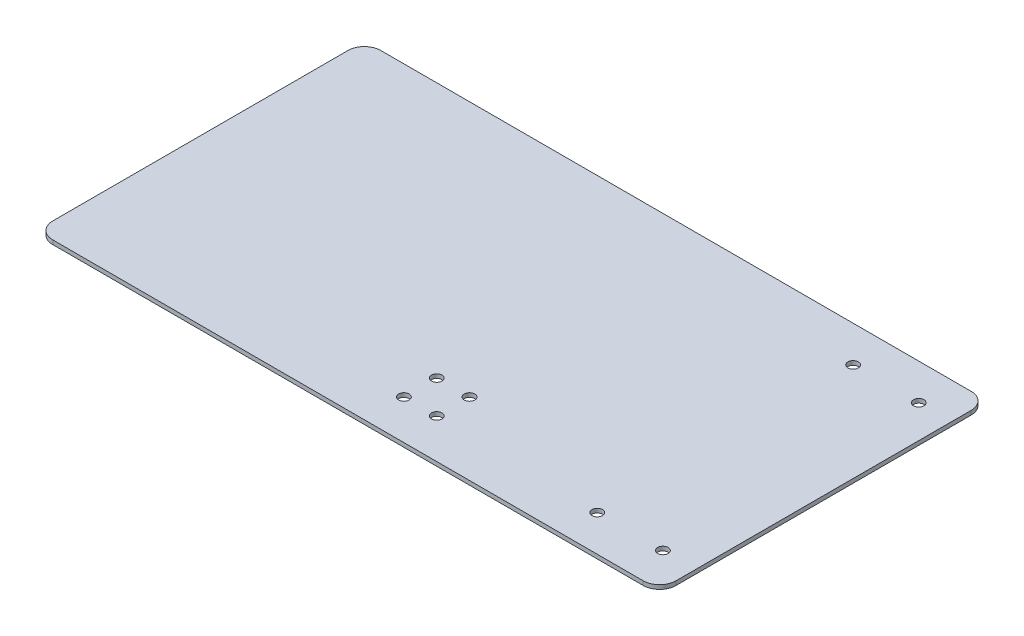
SolidWorks part; units mm, degrees
ref_plane "Front Plane" through (0, 0, 0) normal (0, 0, 1) x (1, 0, 0)
ref_plane "Top Plane" through (0, 0, 0) normal (0, 1, 0) x (1, 0, 0)
ref_plane "Right Plane" through (0, 0, 0) normal (1, 0, 0) x (0, 0, -1)
sketch "Sketch1" plane through (0, 0, 0) normal (0, 1, 0) x (1, 0, 0)
  line L0 (120.65, -35.4965) -> (19.05, -35.4965) construction
  line L1 (-120.65, 63.5) -> (120.65, 63.5)
  line L2 (-120.65, 63.5) -> (-120.65, -63.5)
  line L3 (-120.65, -63.5) -> (120.65, -63.5)
  line L4 (120.65, 63.5) -> (120.65, -63.5)
  line L5 (-120.65, 63.5) -> (120.65, -63.5) construction
  line L6 (-120.65, -63.5) -> (120.65, 63.5) construction
  line L7 (120.65, -49.53) -> (107.95, -49.53) construction
  line L8 (107.95, -49.53) -> (82.55, -49.53) construction
  line L9 (120.65, 49.53) -> (107.95, 49.53) construction
  line L10 (107.95, 49.53) -> (82.55, 49.53) construction
  line L11 (19.05, -35.4965) -> (6.35, -35.4965) construction
  line L12 (6.35, -35.4965) -> (6.35, -48.1965) construction
  line L13 (6.35, -48.1965) -> (19.05, -48.1965) construction
  line L14 (19.05, -48.1965) -> (19.05, -35.4965) construction
  circle A0 centre (82.55, 49.53) radius 2.032
  circle A1 centre (82.55, -49.53) radius 2.032
  circle A2 centre (107.95, -49.53) radius 2.032
  circle A3 centre (107.95, 49.53) radius 2.032
  circle A4 centre (19.05, -35.4965) radius 2.032
  circle A5 centre (6.35, -35.4965) radius 2.032
  circle A6 centre (6.35, -48.1965) radius 2.032
  circle A7 centre (19.05, -48.1965) radius 2.032
  point P0 (0, 0)
  dimension "D7" = 4.064
  dimension "D1" = 241.3
  dimension "D2" = 127
  dimension "D3" = 12.7
  dimension "D4" = 25.4
  dimension "D5" = 13.97
  dimension "D6" = 13.97
  dimension "D8" = 101.6
  dimension "D9" = 12.7
  dimension "D10" = 28.0035
  dimension "D11" = 12.7
extrude "Boss-Extrude1" add sketch "Sketch1" along normal blind 1.5875 contours L1 L3 L4 A7 A6 A5 A4 A3 A2 A1 A0 region at (-0.1834, 0, -0.0711)
sketch "Sketch2" [suppressed] plane through (0, 1.5875, 0) normal (0, 1, 0) x (1, 0, 0)
  line L0 (31.75, 63.5) -> (31.75, -63.5)
  line L1 (-120.65, 63.5) -> (120.65, 63.5) construction
  line L2 (-120.65, -63.5) -> (120.65, -63.5) construction
  circle A0 centre (44.45, -48.1965) radius 2.032 construction
  line M11 (120.65, 63.5) -> (-120.65, 63.5)
  line M12 (-120.65, 63.5) -> (-120.65, -63.5)
  line M13 (-120.65, -63.5) -> (120.65, -63.5)
  dimension "D1" = 12.7
extrude "Cut-Extrude1" [suppressed] cut sketch "Sketch2" against normal through all contours L0 M11 M12 M13
fillet "Fillet1" radius 6.35 4 edges at (-120.65, 0.7937, -63.5) (-120.65, 0.7937, 63.5) (120.65, 0.7937, -63.5) (120.65, 0.7937, 63.5)
fillet "Fillet2" [suppressed] radius 6.35
